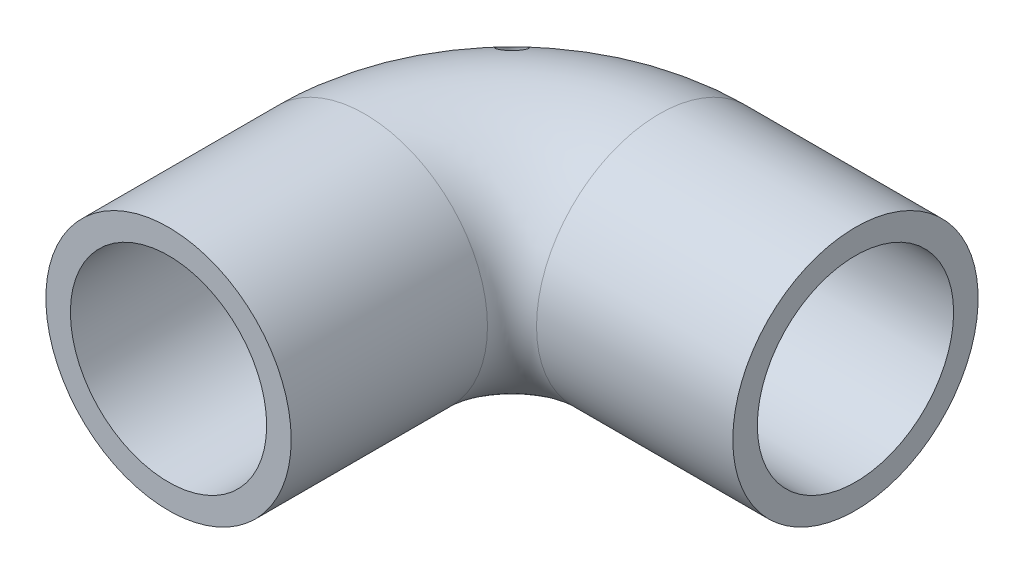
SolidWorks part; units mm, degrees
ref_plane "Front Plane" through (0, 0, 0) normal (0, 0, 1) x (1, 0, 0)
ref_plane "Top Plane" through (0, 0, 0) normal (0, 1, 0) x (1, 0, 0)
ref_plane "Right Plane" through (0, 0, 0) normal (1, 0, 0) x (0, 0, -1)
sketch "Sketch1" plane through (0, 0, 0) normal (0, 1, 0) x (1, 0, 0)
  line L3 (0, -50) -> (0, -90)
  line L4 (30, -20) -> (70, -20)
  arc A0 (0, -50) -> (30, -20) centre (30, -50) cw
  dimension "D3" = 30
ref_plane "Plane1" through (0, 0, 90) normal (0, 0, 1) x (1, 0, 0)
sketch "Sketch2" plane through (0, 0, 90) normal (0, 0, 1) x (1, 0, 0)
  circle A0 centre (0, 0) radius 25
  dimension "D1" = 50
sweep "Sweep7" add profiles "Sketch2" path "Sketch1"
shell "Shell3" thickness 5 removed face at (70, 0, 45) removed face at (25, 0, 90)
sketch "Sketch3" plane through (0, 0, 0) normal (0, 1, 0) x (1, 0, 0)
  circle A0 centre (0, -20) radius 2.5
  dimension "D1" = 5
extrude "Cut-Extrude2" cut sketch "Sketch3" along normal through all and the other way blind 96 contours A0
